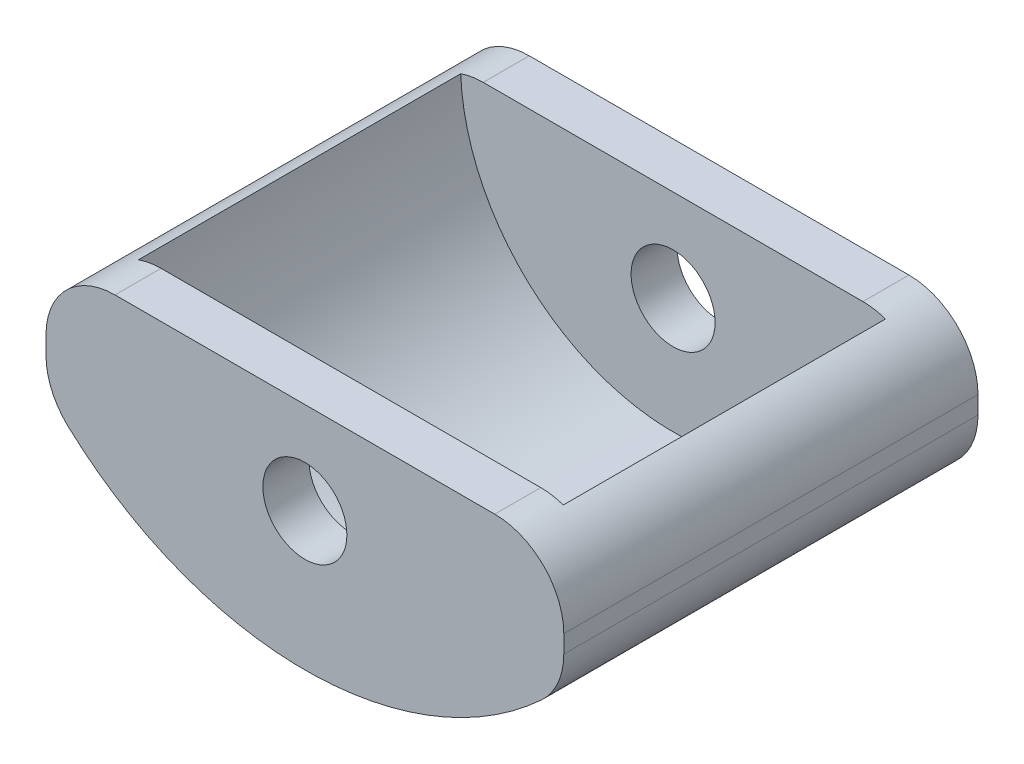
SolidWorks part; units mm, degrees
ref_plane "Front Plane" through (0, 0, 0) normal (0, 0, 1) x (1, 0, 0)
ref_plane "Top Plane" through (0, 0, 0) normal (0, 1, 0) x (1, 0, 0)
ref_plane "Right Plane" through (0, 0, 0) normal (1, 0, 0) x (0, 0, -1)
sketch "Sketch1" plane through (0, 0, 0) normal (0, 1, 0) x (1, 0, 0)
  line L1 (-11.25, 9) -> (11.25, 9)
  line L2 (-11.25, 9) -> (-11.25, -9)
  line L3 (-11.25, -9) -> (11.25, -9)
  line L4 (11.25, 9) -> (11.25, -9)
  dimension "D1" = 18
  dimension "D2" = 9
  dimension "D3" = 22.5
  dimension "D4" = 11.25
extrude "Boss-Extrude1" add sketch "Sketch1" along normal blind 10
sketch "Sketch2" plane through (0, 0, 9) normal (0, 0, 1) x (1, 0, 0)
  line L0 (-11.25, 10) -> (-11.25, 0) construction
  line L1 (11.25, 10) -> (11.25, 0) construction
  line L2 (-11.25, 5) -> (-11.25, 0)
  line L3 (-11.25, 0) -> (11.25, 0)
  line L4 (11.25, 0) -> (11.25, 5)
  line L5 (-11.25, 10) -> (11.25, 10) construction
  arc A0 (-11.25, 5) -> (11.25, 5) centre (0, 15.1866) ccw
  circle A1 centre (0, 6) radius 1.825
  point P19 (0, 0.01)
  dimension "D1" = 3.65
  dimension "D2" = 11.25
  dimension "D3" = 4
  dimension "D4" = 5.99
extrude "Cut-Extrude1" cut sketch "Sketch2" against normal through all and the other way through all
ref_plane "Plane1" through (0, 0, 7) normal (0, 0, 1) x (1, 0, 0)
sketch "Sketch3" plane through (0, 0, 7) normal (0, 0, 1) x (1, 0, 0)
  line L5 (-7.5, 10) -> (7.5, 10)
  line L6 (11.25, 10) -> (-11.25, 10) construction
  line L7 (-5.7661, 10.0479) -> (5.7661, 10.0479)
  arc A3 (-7.5, 10) -> (7.5, 10) centre (0, 10.2071) ccw construction
  arc A4 (-9.2339, 9.9521) -> (9.2339, 9.9521) centre (0, 10.2071) ccw
  arc A5 (-5.7661, 10.0479) -> (5.7661, 10.0479) centre (0, 10.2071) ccw
  arc A6 (-5.7661, 10.0479) -> (-9.2339, 9.9521) centre (-7.5, 10) ccw
  arc A7 (9.2339, 9.9521) -> (5.7661, 10.0479) centre (7.5, 10) ccw
  arc A8 (-5.7661, 10.0479) -> (5.7661, 10.0479) centre (0, 10.2071) ccw
  point P5 (0, 2.7043)
  point P16 (0, 10)
  dimension "D3" = 5.7683
  dimension "D1" = 15
  dimension "D2" = 3.75
  dimension "D4" = 7.2957
extrude "Cut-Extrude2" cut sketch "Sketch3" against normal blind 14 contours A5 A7 A4 A6
sketch "Sketch4" plane through (0, 10, 0) normal (0, 1, 0) x (1, 0, 0)
  line L1 (-5.7645, 7) -> (5.7645, 7)
  line L2 (-5.7645, 7) -> (-5.7645, -7)
  line L3 (-5.7645, -7) -> (5.7645, -7)
  line L4 (5.7645, 7) -> (5.7645, -7)
extrude "Cut-Extrude3" cut sketch "Sketch4" against normal up to surface (7.011 mm away) up to face at (0, 5.4609, 0)
fillet "Fillet1" radius 3 4 edges at (11.25, 5, 0) (-11.25, 5, 0) (11.25, 10, 0) (-11.25, 10, 0)
